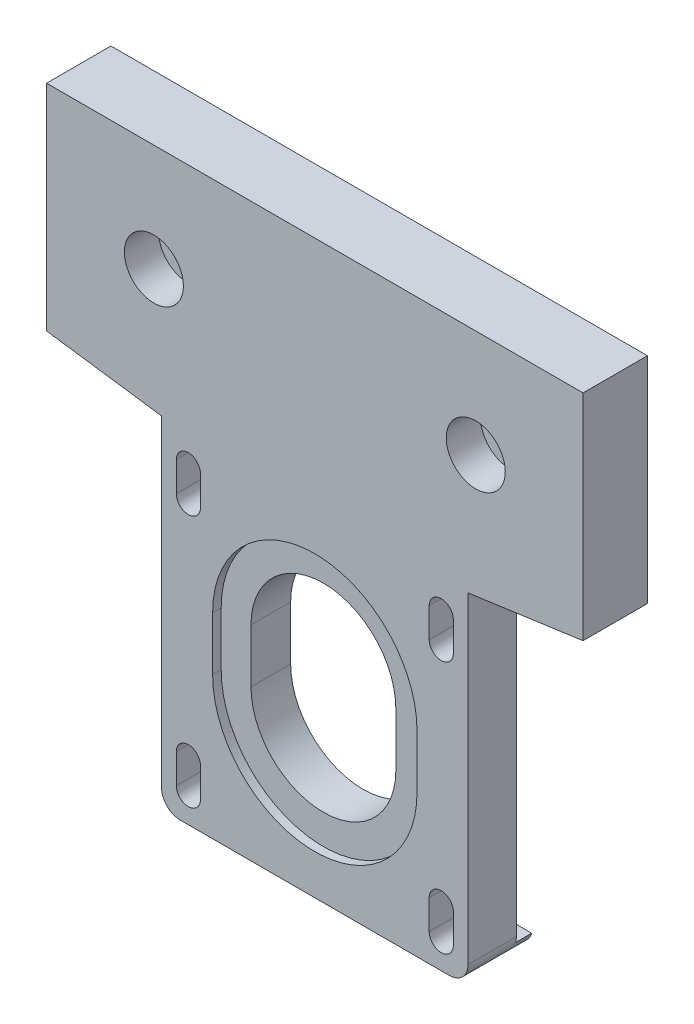
SolidWorks part; units mm, degrees
material "3.1355 (EN-AW 2024)"
ref_plane "Спереди" through (0, 0, 0) normal (0, 0, 1) x (1, 0, 0)
ref_plane "Сверху" through (0, 0, 0) normal (0, 1, 0) x (1, 0, 0)
ref_plane "Справа" through (0, 0, 0) normal (1, 0, 0) x (0, 0, -1)
sketch "Эскиз1" plane through (0, 0, 0) normal (0, 0, 1) x (1, 0, 0)
  line L0 (-50, 0) -> (50, 0)
  line L1 (50, 0) -> (50, -40)
  line L2 (50, -40) -> (28.575, -43)
  line L3 (28.575, -43) -> (28.575, -103)
  line L4 (25.075, -106.5) -> (-25.075, -106.5)
  line L5 (-28.575, -103) -> (-28.575, -43)
  line L6 (-28.575, -43) -> (-50, -40)
  line L7 (-50, -40) -> (-50, 0)
  arc A0 (28.575, -103) -> (25.075, -106.5) centre (25.075, -103) cw
  arc A1 (-25.075, -106.5) -> (-28.575, -103) centre (-25.075, -103) cw
  point P2 (0, 0)
  point P9 (0, -106.5)
  point P13 (28.575, -106.5)
  point P16 (-28.575, -106.5)
  dimension "D5" = 3.5
  dimension "D1" = 100
  dimension "D2" = 57.15
  dimension "D3" = 40
  dimension "D4" = 60
  dimension "D6" = 3
extrude "Бобышка-Вытянуть1" add sketch "Эскиз1" against normal blind 12
hole_wizard "Цековка для  винта с внутренним шестигранником M61" positions "Эскиз2" profile "Эскиз3" counterbore size "M6" standard "DIN" end condition through all
sketch "Эскиз2" plane through (0, 0, 0) normal (0, 0, 1) x (1, 0, 0)
  line L0 (-30, -20) -> (0, -20) construction
  line L1 (0, -20) -> (30, -20) construction
  line L2 (-50, 0) -> (-50, -40) construction
  point P2 (-30, -20)
  point P4 (30, -20)
  point P14 (-50, -20)
  dimension "D1" = 30
sketch "Эскиз3" plane through (-30, -20, 0) normal (1, 0, 0) x (0, -1, 0)
  line L0 (0, 0) -> (0, 12)
  line L1 (0, 12) -> (3.3, 12)
  line L3 (3.3, 12) -> (3.3, 6.4)
  line L4 (3.3, 6.4) -> (5.5, 6.4)
  line L5 (5.5, 6.4) -> (5.5, 0)
  line L7 (5.5, 0) -> (0, 0)
  line L11 (0, -6.35) -> (0, 107.95) construction
  dimension "Диаметр сквозного отверстия" = 6.6
  dimension "Глубина сквозного отверстия" = 12
  dimension "Диаметр цековки" = 11
  dimension "Глубина цековки" = 6.4
sketch "Эскиз4" plane through (0, 0, -12) normal (0, 0, -1) x (-1, 0, 0)
  line L3 (-28.575, -43) -> (28.575, -43)
  line L4 (28.575, -43) -> (28.575, -104)
  line L5 (28.575, -104) -> (-28.575, -104)
  line L6 (-28.575, -104) -> (-28.575, -43)
  dimension "D1" = 61
extrude "Вырез-Вытянуть1" cut sketch "Эскиз4" against normal blind 3
sketch "Эскиз12" plane through (0, 0, 0) normal (0, 0, 1) x (1, 0, 0)
  line L0 (-25.075, -106.5) -> (25.075, -106.5) construction
  line L1 (-19.05, -80) -> (-19.05, -70)
  line L2 (19.05, -80) -> (19.05, -70)
  arc A0 (-19.05, -80) -> (19.05, -80) centre (0, -80) ccw
  arc A1 (19.05, -70) -> (-19.05, -70) centre (0, -70) ccw
  dimension "D1" = 19.05
  dimension "D2" = 26.5
  dimension "D3" = 10
extrude "Вырез-Вытянуть2" cut sketch "Эскиз12" against normal blind 1.6
sketch "Эскиз13" plane through (0, 0, -1.6) normal (0, 0, 1) x (1, 0, 0)
  line L0 (-13.5, -80) -> (-13.5, -70)
  line L1 (13.5, -80) -> (13.5, -70)
  arc A0 (-13.5, -80) -> (13.5, -80) centre (0, -80) ccw
  arc A1 (13.5, -70) -> (-13.5, -70) centre (0, -70) ccw
  dimension "D1" = 13.5
extrude "Вырез-Вытянуть3" cut sketch "Эскиз13" against normal through all
hole_wizard "Прорезь с зазором M42" positions "Эскиз7" profile "Эскиз9" size "M4" standard "DIN" slot yes end condition through all
sketch "Эскиз7" plane through (0, 0, 0) normal (0, 0, 1) x (1, 0, 0)
  line L0 (-23.57, -51.43) -> (0, -51.43) construction
  line L1 (0, -51.43) -> (23.57, -51.43) construction
  line L4 (-23.57, -98.57) -> (-23.57, -75) construction
  line L5 (-23.57, -75) -> (-23.57, -51.43) construction
  line L8 (0, -75) -> (0, -51.43) construction
  line L11 (0, -75) -> (-23.57, -75) construction
  line L14 (-23.57, -46.43) -> (-23.57, -56.43) construction
  line L15 (0, -70) -> (0, -80) construction
  point P0 (-23.57, -51.43)
  point P3 (23.57, -51.43)
  point P5 (23.57, -98.57)
  point P7 (-23.57, -98.57)
  point P44 (0, -75)
  dimension "D1" = 47.14
  dimension "D2" = 10
sketch "Эскиз9" plane through (-23.57, -51.43, 0) normal (1, 0, 0) x (0, -1, 0)
  line L0 (0, 0) -> (0, 12)
  line L1 (0, 12) -> (2.25, 12)
  line L2 (2.25, 12) -> (2.25, 0)
  line L5 (2.25, 0) -> (0, 0)
  line L11 (0, -6.35) -> (0, 107.95) construction
  dimension "Диаметр сквозного отверстия" = 4.5
  dimension "Глубина сквозного отверстия" = 12
